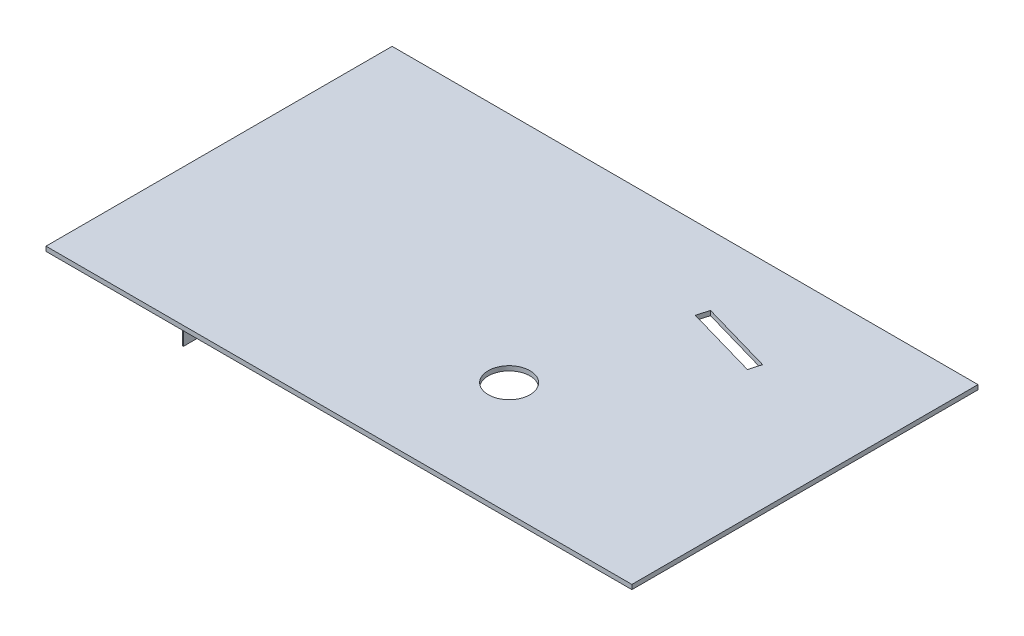
SolidWorks part; units mm, degrees
material "Particle Board"
ref_plane "Front Plane" through (0, 0, 0) normal (0, 0, 1) x (1, 0, 0)
ref_plane "Top Plane" through (0, 0, 0) normal (0, 1, 0) x (1, 0, 0)
ref_plane "Right Plane" through (0, 0, 0) normal (1, 0, 0) x (0, 0, -1)
sketch "Sketch3" plane through (0, 0, 0) normal (0, 1, 0) x (1, 0, 0)
  line L1 (0, 0) -> (-839.8654, 0) construction
  line L2 (0, 0) -> (-451.1992, 260.5) construction
  line L5 (-524, 0) -> (-525.5875, 0)
  line L6 (277.6777, 444.3772) -> (277.6777, 446.248)
  circle A0 centre (0, 0) radius 254 construction
  arc A3 (277.6777, 444.3772) -> (-524, 0) centre (0, 0) ccw
  arc A4 (277.6777, 446.248) -> (-525.5875, 0) centre (0, 0) ccw
  arc A5 (278.5189, 445.7235) -> (-525.5875, 0) centre (0, 0) ccw construction
  dimension "D1" = 524
  dimension "D2" = 1.5875
  dimension "D4" = 122
  dimension "D5" = 508
  dimension "D3" = 30
extrude "Boss-Extrude1" add sketch "Sketch3" along normal blind 50.8
sketch "Sketch4" plane through (0, 50.8, 0) normal (0, 1, 0) x (1, 0, 0)
  line L5 (-852, 567) -> (575, 567)
  line L6 (-852, 567) -> (-852, -276)
  line L7 (-852, -276) -> (575, -276)
  line L8 (575, 567) -> (575, -276)
  dimension "D1" = 276
  dimension "D2" = 852
  dimension "D3" = 567
  dimension "D4" = 575
extrude "Boss-Extrude2" add sketch "Sketch4" against normal blind 11.1125
hole_wizard "Ø20.0mm Dowel Hole1" positions "Sketch6" profile "Sketch7" hole size "Ø20.0" standard "ANSI Metric" end condition through all
sketch "Sketch6" plane through (0, 50.8, 0) normal (0, 1, 0) x (1, 0, 0)
  point P0 (0, 0)
sketch "Sketch7" plane through (0, 50.8, 0) normal (1, 0, 0) x (0, 0, 1)
  line L0 (0, 0) -> (0, 50.8)
  line L1 (0, 50.8) -> (50.8, 50.8)
  line L2 (50.8, 50.8) -> (50.8, 0)
  line L5 (50.8, 0) -> (0, 0)
  line L11 (0, -6.35) -> (0, 107.95) construction
  dimension "Thru Hole Dia." = 101.6
  dimension "Thru Hole Depth" = 50.8
ref_plane "Plane1" through (0, 0, 269.65) normal (0, 0, 1) x (1, 0, 0)
sketch "Sketch8" plane through (0, 0, 0) normal (0, 0, 1) x (1, 0, 0)
  line L0 (-524, 39.6875) -> (-524, 0) construction
  line L1 (-525.5875, 39.6875) -> (-524, 39.6875)
  line L2 (-525.5875, 39.6875) -> (-525.5875, 0)
  line L3 (-525.5875, 0) -> (-524, 0)
  line L4 (-524, 39.6875) -> (-524, 0)
  line L5 (-525.5875, 39.6875) -> (-525.5875, 0) construction
  line L6 (-525.5875, 0) -> (-524, 0) construction
extrude "Boss-Extrude3" add sketch "Sketch8" along normal up to surface (269.65 mm away) up to plane "Plane1"
sketch "Sketch9" plane through (0, 50.8, 0) normal (0, 1, 0) x (1, 0, 0)
  line L0 (270.6691, 346.7379) -> (92.8357, 397.7308)
  line L1 (92.8357, 397.7308) -> (84.5666, 368.8929)
  line L2 (84.5666, 368.8929) -> (262.4, 317.9)
  line L3 (262.4, 317.9) -> (270.6691, 346.7379)
  line L6 (0, 0) -> (575, 0) construction
  line L7 (575, -276) -> (575, 567) construction
  dimension "D1" = 185
  dimension "D2" = 30
  dimension "D3" = 16
  dimension "D4" = 262.4
  dimension "D5" = 317.9
extrude "Cut-Extrude1" cut sketch "Sketch9" against normal through all
sketch "Sketch10" plane through (0, 39.6875, 0) normal (0, 1, 0) x (1, 0, 0)
  line L0 (0, 0) -> (-545.6, 0) construction
  line L1 (0, 0) -> (277.6777, 444.3772) construction
  line L2 (0, 0) -> (195.5256, 509.3615) construction
  line L3 (0, 0) -> (94.7424, 537.3111) construction
  circle A0 centre (0, 0) radius 545.6 construction
  dimension "D1" = 11
  dimension "D2" = 11
